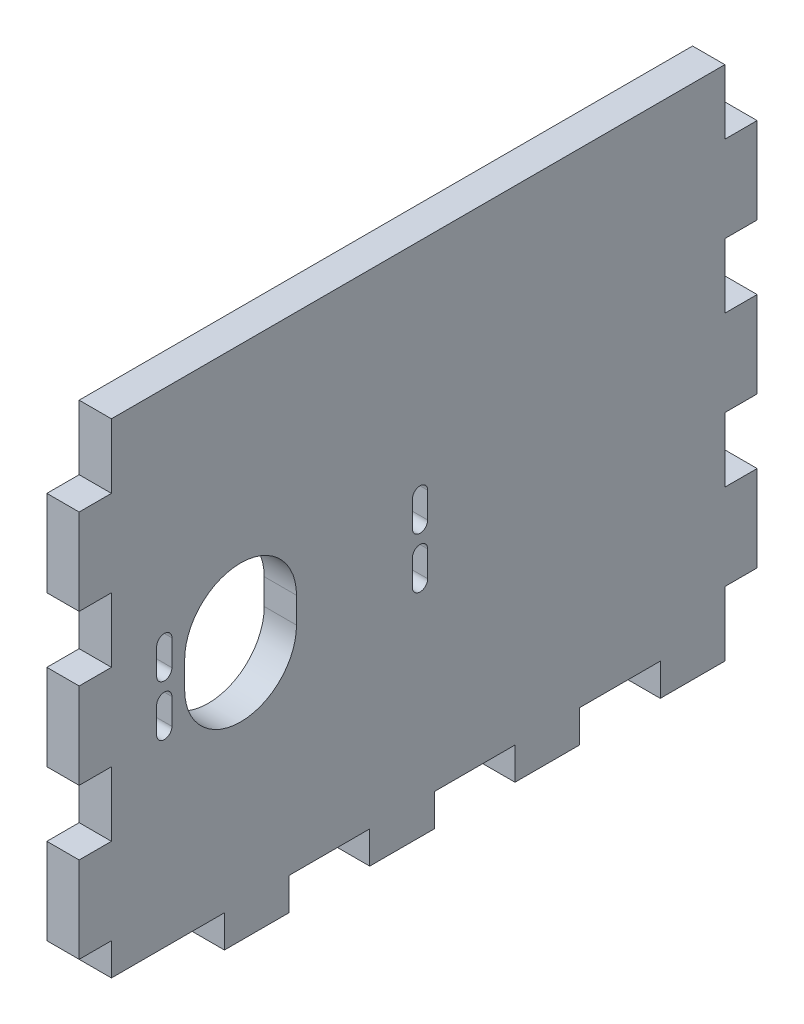
SolidWorks part; units mm, degrees
material "Acrylic (Medium-high impact)"
ref_plane "Front" through (0, 0, 0) normal (0, 0, 1) x (1, 0, 0)
ref_plane "Top" through (0, 0, 0) normal (0, 1, 0) x (1, 0, 0)
ref_plane "Right" through (0, 0, 0) normal (1, 0, 0) x (0, 0, -1)
sketch "Sketch1" plane through (0, 0, 0) normal (0, 0, 1) x (1, 0, 0)
  line L0 (0, 143.002) -> (0, -143.002) construction
  line L1 (-3.302, 133.858) -> (-3.302, -143.002)
  line L2 (-3.302, -143.002) -> (3.302, -143.002)
  line L3 (3.302, 143.002) -> (3.302, -143.002)
  line L4 (3.302, 143.002) -> (-16.256, 143.002)
  line L5 (-5.842, 136.398) -> (-16.256, 136.398)
  line L6 (-16.256, 143.002) -> (-16.256, 136.398)
  line L8 (-28.956, 155.448) -> (16.002, 155.448)
  line L9 (-28.956, 155.448) -> (-28.956, -149.352)
  line L10 (-28.956, -149.352) -> (16.002, -149.352)
  line L11 (16.002, 155.448) -> (16.002, -149.352)
  arc A0 (-3.302, 133.858) -> (-5.842, 136.398) centre (-5.842, 133.858) ccw
  point P2 (0, -143.002)
  point P11 (0, 0)
  dimension "D5" = 2.54
  dimension "D1" = 6.604
  dimension "D2" = 12.954
  dimension "D3" = 6.604
  dimension "D4" = 286.004
  dimension "D6" = 304.8
  dimension "D7" = 6.35
  dimension "D8" = 12.7
  dimension "D9" = 12.7
extrude "Boss-Extrude1" add sketch "Sketch1" along normal blind 6.35
sketch "Sketch2" plane through (16.002, 0, 0) normal (1, 0, 0) x (0, 0, -1)
  line L0 (-6.35, -149.352) -> (-6.35, 155.448) construction
  line L1 (-6.35, -47.752) -> (127, -47.752)
  line L2 (-6.35, -47.752) -> (-6.35, -149.352)
  line L3 (-6.35, -149.352) -> (127, -149.352)
  line L4 (127, -47.752) -> (127, -149.352)
  line L5 (14.4, -101.092) -> (14.4, -96.012)
  line L6 (36.4, -96.012) -> (36.4, -101.092)
  line L7 (8.4, -116.592) -> (8.4, -111.512)
  line L8 (11.4, -116.592) -> (11.4, -111.512)
  line L9 (8.4, -85.592) -> (8.4, -80.512)
  line L10 (11.4, -85.592) -> (11.4, -80.512)
  line L11 (25.4, -96.012) -> (25.4, -101.092) construction
  line L12 (42.4, -116.592) -> (42.4, -111.512)
  line L13 (39.4, -116.592) -> (39.4, -111.512)
  line L14 (39.4, -85.592) -> (39.4, -80.512)
  line L15 (42.4, -85.592) -> (42.4, -80.512)
  line L16 (0, -149.352) -> (0, 155.448) construction
  line L17 (123.825, -60.452) -> (123.825, -77.3853) construction
  line L18 (127, -47.752) -> (120.65, -47.752)
  line L19 (127, -47.752) -> (127, -60.452)
  line L20 (127, -60.452) -> (120.65, -60.452)
  line L21 (120.65, -47.752) -> (120.65, -60.452)
  line L22 (127, -107.0187) -> (120.65, -107.0187)
  line L23 (127, -107.0187) -> (127, -119.7187)
  line L24 (127, -119.7187) -> (120.65, -119.7187)
  line L25 (120.65, -107.0187) -> (120.65, -119.7187)
  line L26 (127, -136.652) -> (120.65, -136.652)
  line L27 (127, -136.652) -> (127, -149.352)
  line L28 (127, -149.352) -> (120.65, -149.352)
  line L29 (120.65, -136.652) -> (120.65, -149.352)
  line L30 (127, -77.3853) -> (120.65, -77.3853)
  line L31 (127, -77.3853) -> (127, -90.0853)
  line L32 (127, -90.0853) -> (120.65, -90.0853)
  line L33 (120.65, -77.3853) -> (120.65, -90.0853)
  line L34 (123.825, -90.0853) -> (123.825, -107.0187) construction
  line L35 (123.825, -119.7187) -> (123.825, -136.652) construction
  line L36 (10.4, -93.552) -> (60.7, -93.552) construction
  line L37 (60.7, -93.552) -> (60.7, -103.552) construction
  line L38 (60.7, -103.552) -> (10.4, -103.552) construction
  line L39 (10.4, -103.552) -> (10.4, -93.552) construction
  line L40 (8.9, -93.552) -> (8.9, -96.092)
  line L41 (11.9, -96.092) -> (11.9, -93.552)
  line L42 (11.9, -93.552) -> (11.9, -91.012)
  line L43 (8.9, -91.012) -> (8.9, -93.552)
  line L44 (8.9, -106.092) -> (8.9, -101.012)
  line L45 (11.9, -101.012) -> (11.9, -106.092)
  line L46 (62.2, -91.012) -> (62.2, -96.092)
  line L47 (59.2, -96.092) -> (59.2, -91.012)
  line L48 (62.2, -106.092) -> (62.2, -101.012)
  line L49 (59.2, -101.012) -> (59.2, -106.092)
  arc A0 (14.4, -101.092) -> (36.4, -101.092) centre (25.4, -101.092) ccw
  arc A1 (36.4, -96.012) -> (14.4, -96.012) centre (25.4, -96.012) ccw
  arc A2 (8.4, -116.592) -> (11.4, -116.592) centre (9.9, -116.592) ccw
  arc A3 (11.4, -111.512) -> (8.4, -111.512) centre (9.9, -111.512) ccw
  arc A4 (8.4, -85.592) -> (11.4, -85.592) centre (9.9, -85.592) ccw
  arc A5 (11.4, -80.512) -> (8.4, -80.512) centre (9.9, -80.512) ccw
  arc A6 (42.4, -116.592) -> (39.4, -116.592) centre (40.9, -116.592) cw
  arc A7 (39.4, -111.512) -> (42.4, -111.512) centre (40.9, -111.512) cw
  arc A8 (42.4, -85.592) -> (39.4, -85.592) centre (40.9, -85.592) cw
  arc A9 (39.4, -80.512) -> (42.4, -80.512) centre (40.9, -80.512) cw
  circle A10 centre (10.4, -93.552) radius 1.5
  circle A11 centre (60.7, -93.552) radius 1.5
  circle A12 centre (10.4, -103.552) radius 1.5
  circle A13 centre (60.7, -103.552) radius 1.5
  arc A14 (8.9, -96.092) -> (11.9, -96.092) centre (10.4, -96.092) ccw
  arc A15 (11.9, -91.012) -> (8.9, -91.012) centre (10.4, -91.012) ccw
  arc A16 (8.9, -101.012) -> (11.9, -101.012) centre (10.4, -101.012) cw
  arc A17 (11.9, -106.092) -> (8.9, -106.092) centre (10.4, -106.092) cw
  arc A18 (62.2, -96.092) -> (59.2, -96.092) centre (60.7, -96.092) cw
  arc A19 (59.2, -91.012) -> (62.2, -91.012) centre (60.7, -91.012) cw
  arc A20 (62.2, -101.012) -> (59.2, -101.012) centre (60.7, -101.012) ccw
  arc A21 (59.2, -106.092) -> (62.2, -106.092) centre (60.7, -106.092) ccw
  point P44 (25.4, -98.552)
  point P47 (-6.35, -98.552)
  point P71 (10.4, -98.552)
  point P72 (14.4, -98.552)
  point P100 (0, 0)
  point P101 (52.05, -89.861)
  point P102 (52.05, -88.313)
  point P103 (62.2, -93.552)
  point P104 (52.05, -105.5901)
  point P105 (62.2, -103.552)
  point P106 (11.9, -103.552)
  point P107 (1.75, -100.9463)
  point P108 (52.05, -101.0961)
  point P109 (57.279, -91.012)
  line M17 (0, -149.352) -> (0, 155.448)
  line M19 (-6.35, 155.448) -> (-6.35, -149.352)
  line M20 (-6.35, -149.352) -> (0, -149.352)
  dimension "D1" = 22
  dimension "D6" = 1.5
  dimension "D10" = 1.5
  dimension "D18" = 3
  dimension "D2" = 5.08
  dimension "D3" = 5.08
  dimension "D4" = 15.5
  dimension "D5" = 15.5
  dimension "D7" = 15.5
  dimension "D8" = 15.5
  dimension "D9" = 5.08
  dimension "D11" = 25.4
  dimension "D12" = 50.8
  dimension "D13" = 101.6
  dimension "D14" = 12.7
  dimension "D15" = 6.35
  dimension "D16" = 10
  dimension "D17" = 50.3
  dimension "D19" = 5.08
  dimension "D20" = 5.08
  dimension "D21" = 15
extrude "Boss-Extrude2" add sketch "Sketch2" against normal blind 6.35 contours L33 L30 L4 L20 L21 L1 L3 L29 L26 L24 L25 L22 L32 A5 L10 A4 L9 A3 L8 A2 L7 A1 L6 A0 L5 L13 A7 L12 A6 L14 A9 L15 A8 M17 | L1 M19 M20 M17 | L10 A5 L9 A4 | A9 L14 A8 L15 | A7 L13 A6 L12 | L8 A3 L7 A2 region at (16.002, -98.552, -63.9345) region at (16.002, -98.552, 3.175) region at (16.002, -114.052, -9.9) region at (16.002, -83.052, -9.9) region at (16.002, -114.052, -40.9) region at (16.002, -83.052, -40.9)
sketch "Sketch3" plane through (9.652, 0, 0) normal (-1, 0, 0) x (0, 0, 1)
  line L0 (-120.65, -136.652) -> (-120.65, -149.352) construction
  line L1 (-120.65, -143.002) -> (0, -143.002)
  line L2 (-120.65, -143.002) -> (-120.65, -149.352)
  line L3 (-120.65, -149.352) -> (0, -149.352)
  line L4 (0, -143.002) -> (0, -149.352)
  dimension "D1" = 6.35
extrude "Boss-Extrude3" add sketch "Sketch3" along normal up to surface (38.608 mm away) up to face at (-28.956, 3.048, 3.175)
sketch "Sketch4" plane through (0, -149.352, 0) normal (0, -1, 0) x (1, 0, 0)
  line L0 (9.652, -22.225) -> (9.652, -34.925)
  line L1 (16.002, 6.35) -> (9.652, 6.35)
  line L2 (16.002, 6.35) -> (16.002, -6.35)
  line L3 (16.002, -6.35) -> (9.652, -6.35)
  line L4 (9.652, 6.35) -> (9.652, -6.35)
  line L5 (16.002, -22.225) -> (9.652, -22.225)
  line L6 (16.002, -22.225) -> (16.002, -34.925)
  line L7 (16.002, -34.925) -> (9.652, -34.925)
  line L8 (9.652, -50.8) -> (9.652, -63.5)
  line L9 (16.002, -50.8) -> (9.652, -50.8)
  line L10 (16.002, -50.8) -> (16.002, -63.5)
  line L11 (16.002, -63.5) -> (9.652, -63.5)
  line L12 (9.652, -79.375) -> (9.652, -92.075)
  line L13 (16.002, -79.375) -> (9.652, -79.375)
  line L14 (16.002, -79.375) -> (16.002, -92.075)
  line L15 (16.002, -92.075) -> (9.652, -92.075)
  line L16 (9.652, -107.95) -> (9.652, -120.65)
  line L17 (16.002, -107.95) -> (9.652, -107.95)
  line L18 (16.002, -107.95) -> (16.002, -120.65)
  line L19 (16.002, -120.65) -> (9.652, -120.65)
  line L36 (-6.477, 6.35) -> (-6.477, -120.65) construction
  line L37 (-28.956, 6.35) -> (16.002, 6.35) construction
  line L38 (-28.956, -120.65) -> (16.002, -120.65) construction
  line L39 (-22.606, 6.35) -> (-22.606, -120.65)
  line L40 (16.002, 6.35) -> (9.652, 6.35)
  line L41 (16.002, 6.35) -> (16.002, -120.65)
  line L42 (16.002, -120.65) -> (9.652, -120.65)
  line L43 (9.652, 6.35) -> (9.652, -120.65)
  line L44 (-28.956, -120.65) -> (-22.606, -120.65)
  line L45 (-28.956, 6.35) -> (-28.956, -120.65)
  line L46 (-28.956, 6.35) -> (-22.606, 6.35)
  line L47 (-28.956, -120.65) -> (-22.606, -120.65)
  line L48 (-28.956, -107.95) -> (-28.956, -120.65)
  line L49 (-28.956, -107.95) -> (-22.606, -107.95)
  line L50 (-22.606, -107.95) -> (-22.606, -120.65)
  line L51 (-28.956, -106.3625) -> (-22.606, -106.3625)
  line L52 (-28.956, -93.6625) -> (-28.956, -106.3625)
  line L53 (-28.956, -93.6625) -> (-22.606, -93.6625)
  line L54 (-22.606, -93.6625) -> (-22.606, -106.3625)
  line L55 (-28.956, -92.075) -> (-22.606, -92.075)
  line L56 (-28.956, -79.375) -> (-28.956, -92.075)
  line L57 (-28.956, -79.375) -> (-22.606, -79.375)
  line L58 (-22.606, -79.375) -> (-22.606, -92.075)
  line L59 (-28.956, -77.7875) -> (-22.606, -77.7875)
  line L60 (-28.956, -65.0875) -> (-28.956, -77.7875)
  line L61 (-28.956, -65.0875) -> (-22.606, -65.0875)
  line L62 (-22.606, -65.0875) -> (-22.606, -77.7875)
  line L63 (-28.956, -120.65) -> (-22.606, -120.65)
  line L64 (-28.956, -107.95) -> (-28.956, -120.65)
  line L65 (-28.956, -107.95) -> (-22.606, -107.95)
  line L66 (-22.606, -107.95) -> (-22.606, -120.65)
  line L67 (-28.956, -92.075) -> (-22.606, -92.075)
  line L68 (-28.956, -79.375) -> (-28.956, -92.075)
  line L69 (-28.956, -79.375) -> (-22.606, -79.375)
  line L70 (-22.606, -79.375) -> (-22.606, -92.075)
  line L71 (-28.956, -63.5) -> (-22.606, -63.5)
  line L72 (-28.956, -50.8) -> (-28.956, -63.5)
  line L73 (-28.956, -50.8) -> (-22.606, -50.8)
  line L74 (-22.606, -50.8) -> (-22.606, -63.5)
  line L75 (-28.956, -34.925) -> (-22.606, -34.925)
  line L76 (-28.956, -22.225) -> (-28.956, -34.925)
  line L77 (-28.956, -22.225) -> (-22.606, -22.225)
  line L78 (-22.606, 6.35) -> (-22.606, -6.35)
  line L79 (-28.956, -6.35) -> (-22.606, -6.35)
  line L80 (-28.956, 6.35) -> (-28.956, -6.35)
  line L81 (-28.956, 6.35) -> (-22.606, 6.35)
  line L82 (-22.606, -22.225) -> (-22.606, -34.925)
  line L83 (-16.129, 3.175) -> (-22.606, 3.175) construction
  line L85 (-28.956, 6.35) -> (-22.606, 6.35)
  line L86 (-28.956, 6.35) -> (-28.956, 0)
  line L87 (-28.956, 0) -> (-22.606, 0)
  line L88 (-22.606, 6.35) -> (-22.606, 0)
  line L92 (9.652, 6.35) -> (9.652, 0)
  line L93 (9.652, 6.35) -> (16.002, 6.35)
  line L94 (16.002, 6.35) -> (16.002, 0)
  line L95 (9.652, 0) -> (16.002, 0)
  line L96 (-28.956, 6.35) -> (16.002, 6.35)
  line L97 (-28.956, 6.35) -> (-28.956, 0)
  line L98 (-28.956, 0) -> (16.002, 0)
  line L99 (16.002, 6.35) -> (16.002, 0)
  line L100 (-9.652, 6.35) -> (-9.652, 0)
  line L101 (-9.652, 0) -> (-3.302, 0)
  line L102 (-3.302, 6.35) -> (-3.302, 0)
  line L103 (-9.652, 6.35) -> (-3.302, 6.35)
  line L104 (-9.779, 0) -> (-16.129, 0)
  line L105 (-9.779, 0) -> (-9.779, 6.35)
  line L106 (-9.779, 6.35) -> (-16.129, 6.35)
  line L107 (-16.129, 0) -> (-16.129, 6.35)
  line L108 (-9.779, 3.175) -> (-3.302, 3.175) construction
  line L109 (-3.302, 6.35) -> (-3.302, 0) construction
  line L111 (-28.956, 6.35) -> (16.002, 6.35)
  line L112 (-28.956, 6.35) -> (-28.956, 0)
  line L113 (-28.956, 0) -> (16.002, 0)
  line L114 (16.002, 6.35) -> (16.002, 0)
  line M38 (16.002, -120.65) -> (16.002, 6.35)
  line M39 (16.002, 6.35) -> (-28.956, 6.35)
  dimension "D1" = 6.35
  dimension "D2" = 12.7
  dimension "D4" = 6.35
  dimension "D5" = 6.35
  dimension "D7" = 6.35
  dimension "D3" = 5
  dimension "D6" = 3
sketch "Sketch6" plane through (0, 0, 6.35) normal (0, 0, 1) x (1, 0, 0)
  line L1 (16.002, -60.452) -> (9.652, -60.452)
  line L2 (16.002, -60.452) -> (16.002, -77.3853)
  line L3 (16.002, -77.3853) -> (9.652, -77.3853)
  line L4 (9.652, -60.452) -> (9.652, -77.3853)
  line L5 (16.002, -90.0853) -> (9.652, -90.0853)
  line L6 (16.002, -90.0853) -> (16.002, -107.0187)
  line L7 (16.002, -107.0187) -> (9.652, -107.0187)
  line L8 (9.652, -90.0853) -> (9.652, -107.0187)
  line L9 (16.002, -119.7187) -> (9.652, -119.7187)
  line L10 (16.002, -119.7187) -> (16.002, -136.652)
  line L11 (16.002, -136.652) -> (9.652, -136.652)
  line L12 (9.652, -119.7187) -> (9.652, -136.652)
  line L13 (-28.956, -149.352) -> (16.002, -149.352) construction
  line L14 (16.002, -47.752) -> (9.652, -47.752)
  line L15 (16.002, -47.752) -> (16.002, -149.352)
  line L16 (16.002, -149.352) -> (9.652, -149.352)
  line L17 (9.652, -47.752) -> (9.652, -149.352)
  line M1 (16.002, -149.352) -> (16.002, 155.448)
  line M4 (-28.956, -149.352) -> (16.002, -149.352)
sketch "Sketch7" plane through (16.002, 0, 0) normal (1, 0, 0) x (0, 0, -1)
  line L1 (-6.35, 180.723) -> (327.0227, 180.723)
  line L2 (-6.35, 180.723) -> (-6.35, -143.002)
  line L3 (-6.35, -143.002) -> (327.0227, -143.002)
  line L4 (327.0227, 180.723) -> (327.0227, -143.002)
  line L5 (-6.35, -149.352) -> (-6.35, 155.448) construction
  line L6 (120.65, -143.002) -> (0, -143.002) construction
  point P10 (160.3364, -143.002)
extrude "Cut-Extrude1" [suppressed] cut sketch "Sketch7" against normal through all
extrude "Cut-Extrude2" [suppressed] cut sketch "Sketch4" against normal blind 6.35
sketch "Sketch8" plane through (0, 0, 6.35) normal (0, 0, 1) x (1, 0, 0)
  line L0 (-28.956, -149.352) -> (16.002, -149.352) construction
  line L1 (9.652, -149.352) -> (-54.2235, -149.352)
  line L2 (9.652, -149.352) -> (9.652, 165.6994)
  line L3 (9.652, 165.6994) -> (-54.2235, 165.6994)
  line L4 (-54.2235, -149.352) -> (-54.2235, 165.6994)
  line L5 (9.652, -60.452) -> (9.652, -77.3853) construction
  line L7 (16.002, -47.752) -> (9.652, -47.752)
  line L8 (16.002, -47.752) -> (16.002, 165.6994)
  line L9 (16.002, 165.6994) -> (9.652, 165.6994)
  line L10 (9.652, -47.752) -> (9.652, 165.6994)
  line M6 (16.002, 155.448) -> (-28.956, 155.448)
  line M7 (-28.956, 155.448) -> (-28.956, -149.352)
  line M8 (-28.956, -149.352) -> (16.002, -149.352)
  line M9 (-16.256, 143.002) -> (3.302, 143.002)
  line M10 (3.302, 143.002) -> (3.302, -143.002)
  line M11 (3.302, -143.002) -> (-3.302, -143.002)
  line M12 (-3.302, -143.002) -> (-3.302, 133.858)
  arc M13 (-3.302, 133.858) -> (-5.842, 136.398) centre (-5.842, 133.858) ccw
  line M14 (-5.842, 136.398) -> (-16.256, 136.398)
  line M15 (-16.256, 136.398) -> (-16.256, 143.002)
extrude "Cut-Extrude4" cut sketch "Sketch8" against normal through all and the other way through all contours L2 M8 M6 M7 M15 M9 M10 M11 M12 M13 M14 | L4 L1 L2 L3 M7 M6 | L10 L7 L8 L9 region at (-11.5135, 2.4233, 6.35) region at (-40.0771, 15.3918, 6.35)
extrude "Cut-Extrude5" cut sketch "Sketch6" against normal blind 6.35 contours L14 L17 L1 M1 | L3 L17 L5 M1 | L7 L17 L9 M1 | L11 L17 M4 M1 region at (12.827, -54.102, 6.35) region at (12.827, -83.7353, 6.35) region at (12.827, -113.3687, 6.35) region at (12.827, -143.002, 6.35)
extrude "Cut-Extrude6" cut sketch "Sketch4<3>" against normal blind 6.35 contours L15 L43 L17 M38 | L11 L43 L13 M38 | L7 L43 L9 M38 | L3 L43 L5 M38 | L4 L95 L41 M39 | L95 L43 L3 M38 region at (12.827, -149.352, -14.2875) region at (12.827, -149.352, -42.8625) region at (12.827, -149.352, -3.175) region at (12.827, -149.352, 3.175) region at (12.827, -149.352, -71.4375) region at (12.827, -149.352, -100.0125)
sketch "Sketch4<3>" plane through (0, -149.352, 0) normal (0, -1, 0) x (1, 0, 0) same geometry as "Sketch4"
